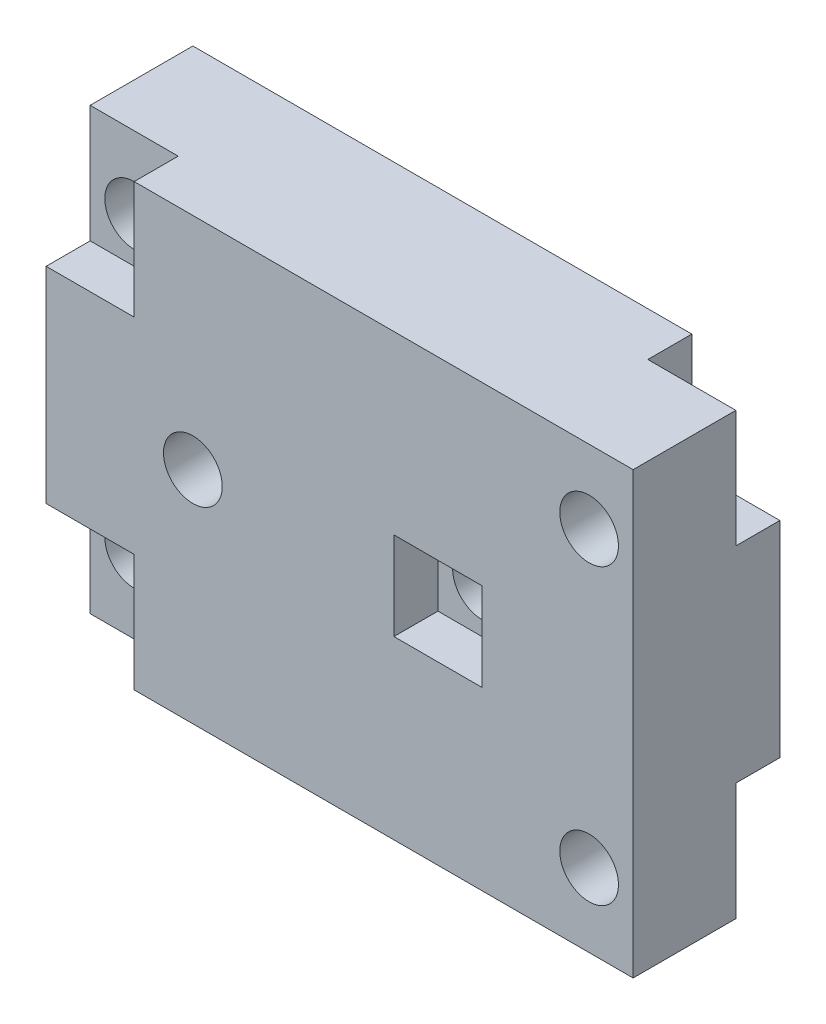
SolidWorks part; units mm, degrees
ref_plane "前视基准面" through (0, 0, 0) normal (0, 0, 1) x (1, 0, 0)
ref_plane "上视基准面" through (0, 0, 0) normal (0, 1, 0) x (1, 0, 0)
ref_plane "右视基准面" through (0, 0, 0) normal (1, 0, 0) x (0, 0, -1)
sketch "草图1" plane through (0, 0, 0) normal (0, 0, 1) x (1, 0, 0)
  line L0 (0, 0) -> (0, 30)
  line L1 (0, 30) -> (40, 30)
  line L2 (40, 30) -> (40, 0)
  line L3 (40, 0) -> (0, 0)
extrude "凸台-拉伸1" add sketch "草图1" along normal blind 5
sketch "草图2" plane through (0, 0, 5) normal (0, 0, 1) x (1, 0, 0)
  circle A0 centre (3, 25) radius 2
  circle A1 centre (3, 5) radius 2
  circle A2 centre (26.7, 15) radius 2
extrude "切除-拉伸1" cut sketch "草图2" against normal blind 5
sketch "草图3" plane through (0, 0, 5) normal (0, 0, 1) x (1, 0, 0)
  line L1 (3, 22) -> (6, 22)
  line L2 (6, 22) -> (6, 30)
  line L3 (40, 30) -> (0, 30) construction
  line L4 (6, 30) -> (0, 30)
  line L5 (0, 30) -> (0, 22)
  line L6 (0, 30) -> (0, 0) construction
  line L7 (0, 22) -> (3, 22)
  line L9 (3, 8) -> (0, 8)
  line L10 (0, 8) -> (0, 0)
  line L11 (0, 0) -> (6, 0)
  line L12 (0, 0) -> (40, 0) construction
  line L13 (6, 0) -> (6, 8)
  line L14 (6, 8) -> (3, 8)
  circle A0 centre (26.7, 15) radius 3
extrude "切除-拉伸2" cut sketch "草图3" against normal blind 2.5
sketch "草图5" plane through (0, 0, 0) normal (0, 0, -1) x (-1, 0, 0)
  line L1 (-40, 30) -> (0, 30)
  line L2 (-40, 30) -> (-40, 0)
  line L3 (-40, 0) -> (0, 0)
  line L4 (0, 30) -> (0, 0)
  circle A0 centre (-26.7, 15) radius 2
  circle A1 centre (-3, 25) radius 2
  circle A2 centre (-3, 5) radius 2
extrude "凸台-拉伸2" add sketch "草图5" along normal blind 3
extrude "切除-拉伸3" cut sketch "草图3<2>" against normal blind 3
sketch "草图3<2>" plane through (0, 0, 5) normal (0, 0, 1) x (1, 0, 0) same geometry as "草图3"
sketch "草图8" plane through (0, 0, -3) normal (0, 0, -1) x (-1, 0, 0)
  circle A0 centre (-37, 25) radius 2
  circle A1 centre (-37, 5) radius 2
  circle A2 centre (-10, 15) radius 2
sketch "草图9" plane through (0, 0, -3) normal (0, 0, -1) x (-1, 0, 0)
  line L1 (-40, 30) -> (0, 30)
  line L2 (-40, 30) -> (-40, 0)
  line L3 (-40, 0) -> (0, 0)
  line L4 (0, 30) -> (0, 0)
  circle A0 centre (-26.7, 15) radius 2
  circle A1 centre (-3, 25) radius 2
  circle A2 centre (-3, 5) radius 2
  circle M1 centre (-3, 25) radius 2
  circle M6 centre (-26.7, 15) radius 2
  circle M7 centre (-3, 5) radius 2
extrude "凸台-拉伸4" add sketch "草图9" along normal blind 2 contours M6 | M1 | M7 | L1 L4 L3 L2 region at (26.7, 15, -3) region at (3, 25, -3) region at (3, 5, -3)
extrude "切除-拉伸5" cut sketch "草图8" against normal blind 10
extrude "切除-拉伸6" cut sketch "草图8<4>" along normal blind 10
sketch "草图8<4>" plane through (0, 0, -3) normal (0, 0, -1) x (-1, 0, 0) same geometry as "草图8"
sketch "草图11" plane through (0, 0, -5) normal (0, 0, -1) x (-1, 0, 0)
  line L1 (-37, 22) -> (-40, 22)
  line L2 (-40, 30) -> (-40, 0) construction
  line L3 (-40, 22) -> (-40, 30)
  line L4 (-40, 30) -> (-34, 30)
  line L5 (-40, 30) -> (0, 30) construction
  line L6 (-34, 30) -> (-34, 22)
  line L7 (-34, 22) -> (-37, 22)
  line L9 (-37, 8) -> (-40, 8)
  line L10 (-40, 8) -> (-40, 0)
  line L11 (-40, 0) -> (-34, 0)
  line L12 (-40, 0) -> (0, 0) construction
  line L13 (-34, 0) -> (-34, 8)
  line L14 (-34, 8) -> (-37, 8)
  line L16 (-10, 18) -> (-7, 18)
  line L17 (-7, 18) -> (-7, 12)
  line L18 (-7, 12) -> (-13, 12)
  line L19 (-13, 12) -> (-13, 18)
  line L20 (-13, 18) -> (-10, 18)
extrude "切除-拉伸7" cut sketch "草图11" against normal blind 3
sketch "草图12" plane through (0, 0, 5) normal (0, 0, 1) x (1, 0, 0)
  line L1 (26.7, 18) -> (29.7, 18)
  line L2 (29.7, 18) -> (29.7, 12)
  line L3 (29.7, 12) -> (23.7, 12)
  line L4 (23.7, 12) -> (23.7, 18)
  line L5 (23.7, 18) -> (26.7, 18)
  circle A0 centre (26.7, 15) radius 3 construction
extrude "切除-拉伸8" cut sketch "草图12" against normal blind 3
